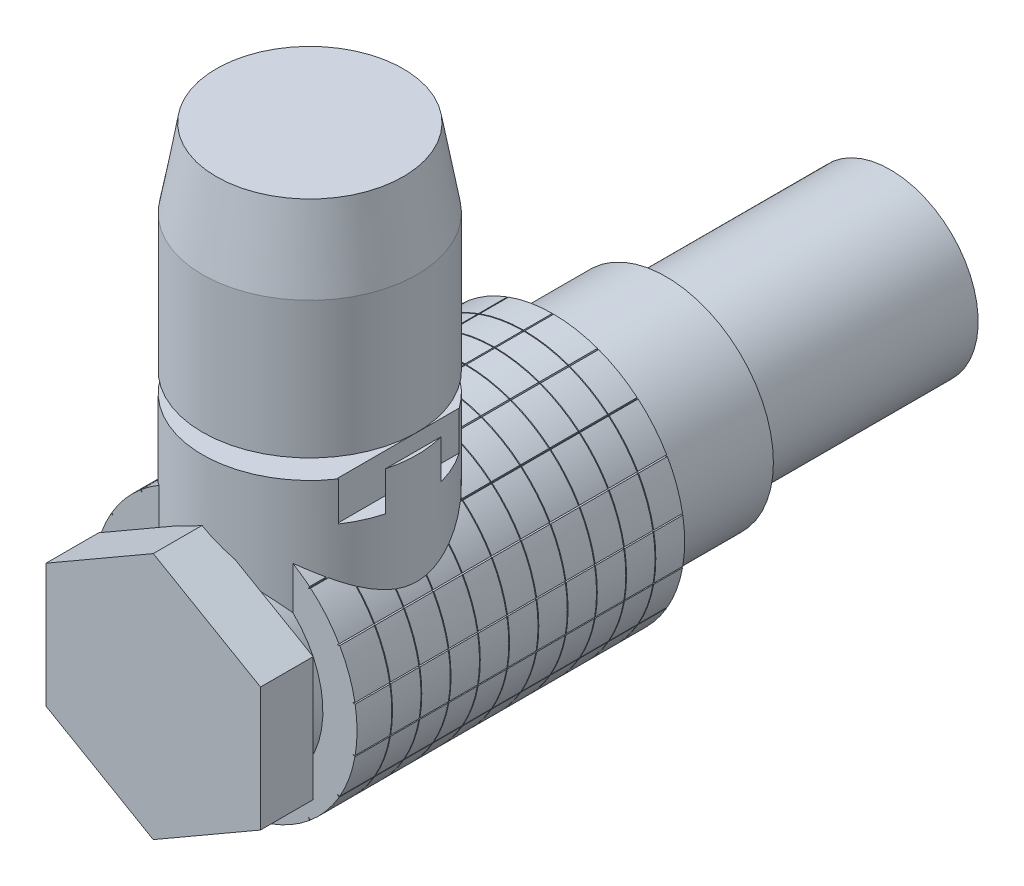
SolidWorks part; units mm, degrees
ref_plane "Plan de face" through (0, 0, 0) normal (0, 0, 1) x (1, 0, 0)
ref_plane "Plan de dessus" through (0, 0, 0) normal (0, 1, 0) x (1, 0, 0)
ref_plane "Plan de droite" through (0, 0, 0) normal (1, 0, 0) x (0, 0, -1)
sketch "Esquisse1" plane through (0, 0, 0) normal (0, 0, 1) x (1, 0, 0)
  circle A0 centre (0, 0) radius 6.75
extrude "Extrusion1" add sketch "Esquisse1" along normal blind 16.8
sketch "Esquisse2" plane through (0, 0, 0) normal (0, 0, -1) x (-1, 0, 0)
  circle A0 centre (0, 0) radius 5.5
extrude "Extrusion2" add sketch "Esquisse2" along normal blind 5.8
sketch "Esquisse3" plane through (0, 0, -5.8) normal (0, 0, -1) x (-1, 0, 0)
  circle A0 centre (0, 0) radius 4.5
extrude "Extrusion3" add sketch "Esquisse3" along normal blind 11.5
sketch "Esquisse4" plane through (0, 0, 0) normal (0, 0, -1) x (-1, 0, 0)
  line L0 (0, 0.05) -> (0, 7.4223) construction
  line L3 (0, 6.625) -> (-0.0463, 6.7979)
  line L4 (0, 6.625) -> (0.0463, 6.7979)
  line L5 (-0.0463, 6.7979) -> (0.0463, 6.7979)
  dimension "D2" = 15
  dimension "D3" = 15
extrude "Extrusion4" cut sketch "Esquisse4" against normal through all
pattern_circular "Répétition circulaire1" count 18 over 360 about axis through (0, 0, 16.8) along (0, 0, -1) of "Extrusion4"
sketch "Esquisse5" plane through (0, 0, 0) normal (1, 0, 0) x (0, 0, -1)
  line L0 (-1.5, 10.3683) -> (-1.5, 3.8822) construction
  line L4 (-1.5, 6.6749) -> (-1.4672, 6.7974)
  line L5 (-1.5, 6.6749) -> (-1.5328, 6.7974)
  line L6 (-1.4672, 6.7974) -> (-1.5328, 6.7974)
  dimension "D3" = 15
  dimension "D4" = 15
revolve "Enlèvement de matière-Révolution1" cut sketch "Esquisse5" angle 360 about axis through (0, 0, 16.8) along (0, 0, -1)
pattern_linear "Répétition linéaire1" count 10 spacing 1.5 along (0, 0, 1) of "Enlèvement de matière-Révolution1"
sketch "Esquisse6" plane through (0, 0, -17.3) normal (0, 0, -1) x (-1, 0, 0)
  circle A0 centre (0, 0) radius 4
extrude "Extrusion5" cut sketch "Esquisse6" against normal blind 11
sketch "Esquisse7" plane through (0, 0, 16.8) normal (0, 0, 1) x (1, 0, 0)
  line L1 (0, 6.3509) -> (-5.5, 3.1754)
  line L2 (-5.5, 3.1754) -> (-5.5, -3.1754)
  line L3 (-5.5, -3.1754) -> (0, -6.3509)
  line L4 (0, -6.3509) -> (5.5, -3.1754)
  line L5 (5.5, -3.1754) -> (5.5, 3.1754)
  line L6 (5.5, 3.1754) -> (0, 6.3509)
  circle A0 centre (0, 0) radius 5.5 construction
extrude "Extrusion6" add sketch "Esquisse7" along normal blind 3.7
sketch "Esquisse8" plane through (0, 0, 16.8) normal (0, 0, 1) x (1, 0, 0)
  circle A0 centre (0, 0) radius 5
extrude "Extrusion7" cut sketch "Esquisse8" along normal blind 1 flip side to cut
sketch "Esquisse9" plane through (0, 0, 0) normal (0, 1, 0) x (1, 0, 0)
  line L0 (5.5, -20.5) -> (0, -20.5) construction
  circle A0 centre (0.0268, -12.5) radius 5.5
  dimension "D1" = 8
extrude "Extrusion8" add sketch "Esquisse9" along normal blind 21.5
chamfer "Chanfrein1" distance 4 angle 10 1 edges at (0.0268, 21.5, 18) first distance on face at (0.0268, 21.5, 18)
ref_plane "Plan1" through (0, 10.5, 0) normal (0, 1, 0) x (-1, 0, 0)
sketch "Esquisse10" plane through (0, 10.5, 0) normal (0, 1, 0) x (-1, 0, 0)
  circle A0 centre (-0.0268, 12.0268) radius 4
extrude "Extrusion9" cut sketch "Esquisse10" against normal blind 1 flip side to cut
sketch "Esquisse11" plane through (0, 9.5, 0) normal (0, 1, 0) x (1, 0, 0)
  line L0 (-4.4732, -8.2136) -> (-4.4732, -15.588)
  line L1 (4.5268, -7.1802) -> (4.5268, -15.588)
  line L2 (-4.4732, -8.2136) -> (-5.4417, -8.2136)
  line L3 (-5.4417, -8.2136) -> (-5.4417, -15.588)
  line L4 (-5.4417, -15.588) -> (-4.4732, -15.588)
  line L5 (4.5268, -7.1802) -> (5.3381, -7.1802)
  line L6 (5.3381, -7.1802) -> (5.3381, -15.588)
  line L7 (5.3381, -15.588) -> (4.5268, -15.588)
  circle A0 centre (0.0268, -12.5) radius 4.7947 construction
  dimension "D1" = 4.5
  dimension "D2" = 4.5
extrude "Extrusion10" cut sketch "Esquisse11" against normal blind 2
